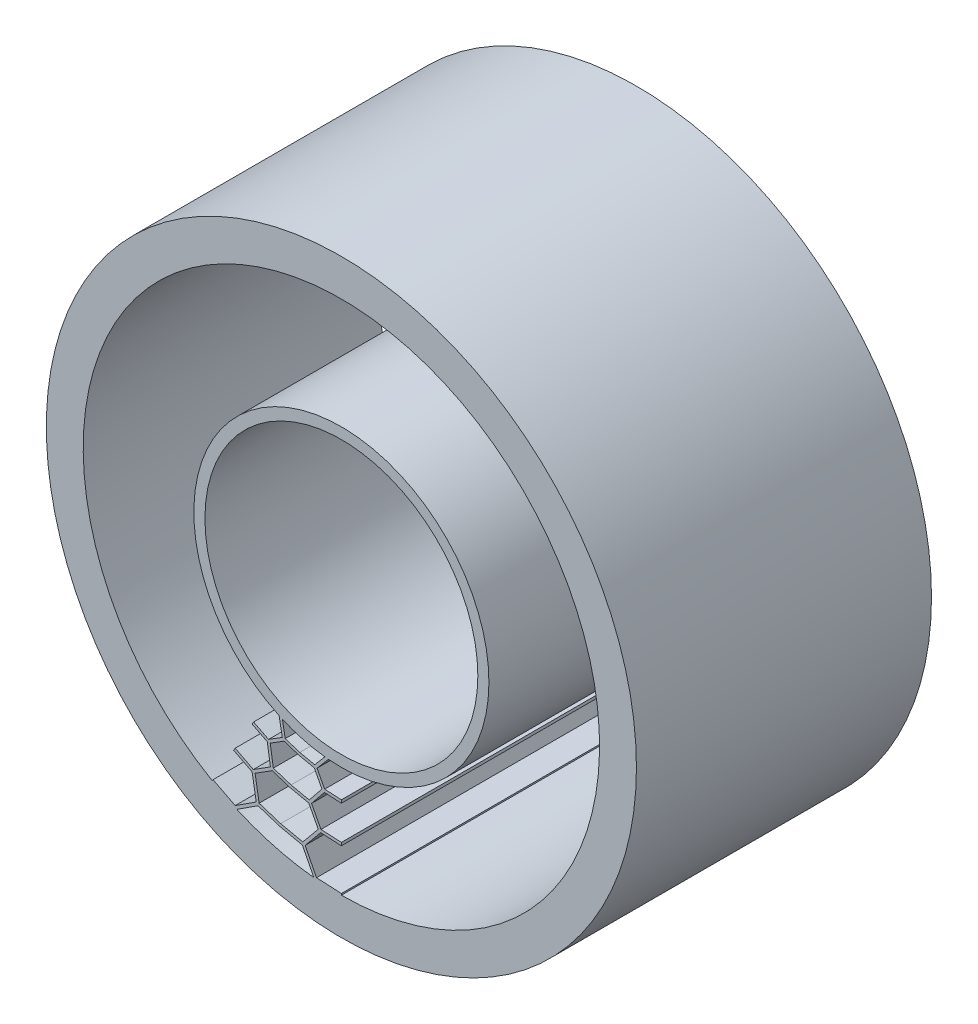
SolidWorks part; units mm, degrees
ref_plane "Front Plane" through (0, 0, 0) normal (0, 0, 1) x (1, 0, 0)
ref_plane "Top Plane" through (0, 0, 0) normal (0, 1, 0) x (1, 0, 0)
ref_plane "Right Plane" through (0, 0, 0) normal (1, 0, 0) x (0, 0, -1)
sketch "Sketch1" plane through (0, 0, 0) normal (0, 0, 1) x (1, 0, 0)
  line L0 (0, 0) -> (0, -40) construction
  line L1 (0, 0) -> (-40, 0) construction
  line L2 (0, 0) -> (-20, -34.641) construction
  line L3 (0, 0) -> (-10.3528, -38.637) construction
  line L4 (0, 0) -> (-4.5684, -34.7006) construction
  line L5 (0, -29) -> (-2.8964, -28.855)
  line L6 (-2.8964, -28.855) -> (-5.1537, -31.5823)
  line L7 (0, 0) -> (-3.4956, -34.825) construction
  line L8 (-5.1537, -31.5823) -> (-8.2822, -30.9096)
  line L9 (-3.4956, -34.825) -> (0, -35) construction
  line L10 (-5.1537, -31.5823) -> (-3.4956, -34.825)
  line L11 (-5.1537, -31.5823) -> (0, 0) construction
  line L12 (0, -32) -> (-3.196, -31.84) construction
  line L13 (-2.8964, -28.855) -> (-4.2786, -26.2195)
  line L14 (-4.2786, -26.2195) -> (-2.3954, -23.8801)
  line L15 (-2.3954, -23.8801) -> (-3.5432, -21.7128)
  line L16 (-3.5432, -21.7128) -> (-1.9975, -19.9)
  line L17 (-2.3954, -23.8801) -> (0, -24)
  line L18 (-4.2786, -26.2195) -> (-6.8759, -25.6611)
  line L19 (-3.5432, -21.7128) -> (-5.694, -21.2504)
  line L20 (-1.7542, -19.9229) -> (-3.3029, -21.7392)
  line L21 (-3.3029, -21.7392) -> (-2.2717, -23.6863)
  line L22 (-2.2717, -23.6863) -> (0, -23.8)
  line L23 (0, -24.2) -> (-2.3034, -24.0847)
  line L24 (-2.3034, -24.0847) -> (-4.0406, -26.2428)
  line L25 (-4.0406, -26.2428) -> (-2.7722, -28.6612)
  line L26 (-2.7722, -28.6612) -> (0, -28.8)
  line L27 (0, -28.8) -> (0, -29.2)
  line L28 (0, -29.2) -> (-2.806, -29.0595)
  line L29 (-2.806, -29.0595) -> (-4.9157, -31.6084)
  line L30 (-4.9157, -31.6084) -> (-3.37, -34.6313)
  line L31 (-3.37, -34.6313) -> (0, -34.8)
  line L32 (-3.6179, -21.4922) -> (-2.2384, -19.8743)
  line L33 (-3.6179, -21.4922) -> (-5.6422, -21.0569)
  line L34 (0, -23.8) -> (0, -24.2)
  line L35 (-5.7458, -21.4438) -> (-3.6763, -21.8888)
  line L36 (-3.6763, -21.8888) -> (-2.6338, -23.8573)
  line L37 (-2.6338, -23.8573) -> (-4.3571, -25.9981)
  line L38 (-4.3571, -25.9981) -> (-6.824, -25.4677)
  line L39 (-6.824, -25.4677) -> (-6.9277, -25.8545)
  line L40 (-6.9277, -25.8545) -> (-4.4122, -26.3954)
  line L41 (-4.4122, -26.3954) -> (-3.1353, -28.83)
  line L42 (-3.1353, -28.83) -> (-5.2304, -31.3612)
  line L43 (-5.2304, -31.3612) -> (-8.2304, -30.7162)
  line L44 (-8.2304, -30.7162) -> (-8.334, -31.1031)
  line L45 (-8.334, -31.1031) -> (-5.2886, -31.7578)
  line L46 (-5.2886, -31.7578) -> (-3.7328, -34.8004)
  line L47 (-3.1147, -20.902) -> (-2.8103, -21.1616) construction
  line L48 (-5.6422, -21.0569) -> (-5.7458, -21.4438)
  line L49 (0, -35.2) -> (0, -34.8)
  line L50 (-3.8523, -33.6881) -> (-4.2085, -33.8702) construction
  line L51 (-3.8548, -29.6993) -> (-3.5466, -29.9543) construction
  line L52 (-3.9304, -27.314) -> (-3.5762, -27.1282) construction
  line L53 (-3.8487, -25.3665) -> (-3.5371, -25.6173) construction
  line L54 (-3.1301, -22.0654) -> (-3.4836, -22.2526) construction
  line L55 (-5.0177, -21.1912) -> (-5.1017, -21.5823) construction
  line L56 (-6.3293, -25.5741) -> (-6.4133, -25.9651) construction
  line L57 (-7.6898, -30.8324) -> (-7.7739, -31.2235) construction
  circle A0 centre (0, 0) radius 20
  circle A2 centre (0, 0) radius 40
  circle A3 centre (0, 0) radius 35
  circle A4 centre (0, 0) radius 29 construction
  circle A5 centre (0, 0) radius 24 construction
  circle A6 centre (0, 0) radius 32 construction
  circle A7 centre (0, 0) radius 26.5663 construction
  circle A8 centre (0, 0) radius 22 construction
  circle A9 centre (0, 0) radius 18.5
  point P12 (-0.0409, -32)
  point P13 (1.8763, -26.5)
  point P14 (0, -22)
  point P67 (-3.7007, -29.8268)
  point P73 (-2.9625, -21.0318)
  point P74 (0, -24)
  point P76 (-5.694, -21.2504)
  point P77 (-6.8759, -25.6611)
  point P78 (-3.7533, -27.2211)
  point P79 (0, -29)
  point P80 (-8.2822, -30.9096)
  point P82 (-4.0304, -33.7791)
  point P85 (-3.6929, -25.4919)
  point P87 (-6.3713, -25.7696)
  point P89 (0, -35)
  point P92 (-3.3069, -22.159)
  point P97 (-5.0597, -21.3867)
  point P98 (-7.7318, -31.028)
  dimension "D1" = 40
  dimension "D2" = 20
  dimension "D3" = 30
  dimension "D4" = 5
  dimension "D7" = 4
  dimension "D8" = 5
  dimension "D13" = 1.5
  dimension "D5" = 15
  dimension "D6" = 7.5
  dimension "D9" = 32
  dimension "D10" = 26.5
  dimension "D11" = 22
  dimension "D12" = 0.4
  dimension "D14" = 3.5
extrude "Boss-Extrude1" add sketch "Sketch1" along normal blind 40 contours L10 A3 L49 L31 L30 L29 L28 L27 L5 L6 | L46 A3 L10 L8 L44 L45 | L43 L44 L8 L6 L13 L18 L39 L40 L41 L42 | L34 L17 L14 L13 L5 L27 L26 L25 L24 L23 | L19 L48 L35 L36 L37 L38 L39 L18 L14 L15 | A0 L16 L15 L17 L34 L22 L21 L20 | A0 L32 L33 L48 L19 L16 region at (-0.0802, -29.1, 0) region at (-1.4449, -28.8609, 0) region at (-4.0867, -30.1676, 0) region at (-4.3801, -33.232, 0) region at (-5.5632, -25.8749, 0) region at (-2.9214, -22.7711, 0) region at (-4.6099, -21.4412, 0)
extrude "Boss-Extrude2" add sketch "Sketch1<6>" along normal up to surface (40 mm away) contours A0 A9 | A2 A3 region at (-2.0581, -19.325, 0) region at (-38.8686, 0, 0) up to face at (-3.4699, -27.0124, 40)
sketch "Sketch1<6>" plane through (0, 0, 0) normal (0, 0, 1) x (1, 0, 0) same geometry as "Sketch1"
mirror "Mirror1" about plane through (0, 0, 40) normal (0.9659, -0.2588, 0) of "Boss-Extrude1"
